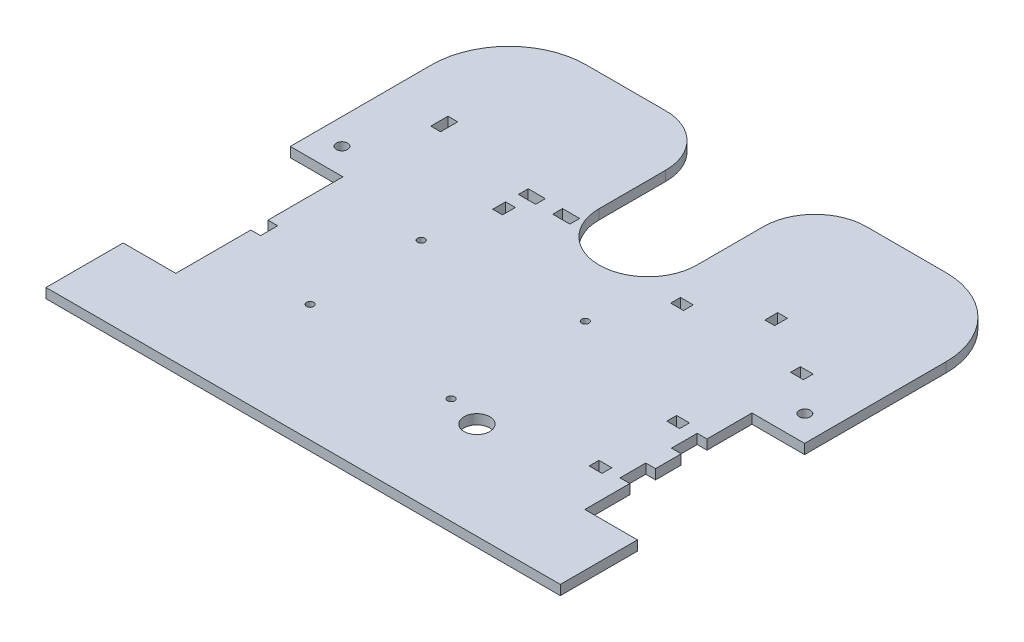
SolidWorks part; units mm, degrees
ref_plane "Front Plane" through (0, 0, 0) normal (0, 0, 1) x (1, 0, 0)
ref_plane "Top Plane" through (0, 0, 0) normal (0, 1, 0) x (1, 0, 0)
ref_plane "Right Plane" through (0, 0, 0) normal (1, 0, 0) x (0, 0, -1)
sketch "Sketch1" plane through (0, 0, 0) normal (0, 1, 0) x (1, 0, 0)
  line L1 (-127, 114.3) -> (127, 114.3)
  line L2 (-127, 114.3) -> (-127, -114.3)
  line L3 (-127, -114.3) -> (127, -114.3)
  line L4 (127, 114.3) -> (127, -114.3)
  line L5 (-127, 114.3) -> (127, -114.3) construction
  line L6 (-127, -114.3) -> (127, 114.3) construction
  point P0 (0, 0)
  dimension "D1" = 254
  dimension "D2" = 228.6
extrude "Boss-Extrude1" add sketch "Sketch1" along normal blind 4.826
sketch "Sketch2" plane through (0, 4.826, 0) normal (0, 1, 0) x (1, 0, 0)
  line L0 (-127, 114.3) -> (-127, -114.3) construction
  line L1 (-127, 6.35) -> (-101, 6.35)
  line L2 (-127, 6.35) -> (-127, -76.2)
  line L3 (-127, -76.2) -> (-101, -76.2)
  line L4 (-101, 6.35) -> (-101, -76.2)
  line L5 (127, -114.3) -> (127, 114.3) construction
  line L6 (127, 6.35) -> (101, 6.35)
  line L7 (127, 6.35) -> (127, -76.2)
  line L8 (127, -76.2) -> (101, -76.2)
  line L9 (101, 6.35) -> (101, -76.2)
  line L10 (-127, -114.3) -> (127, -114.3) construction
  dimension "D1" = 38.1
  dimension "D2" = 38.1
  dimension "D3" = 82.55
  dimension "D4" = 82.55
  dimension "D5" = 26
  dimension "D6" = 26
extrude "Cut-Extrude1" cut sketch "Sketch2" against normal blind 4.826
sketch "Sketch4" plane through (0, 4.826, 0) normal (0, 1, 0) x (1, 0, 0)
  line L0 (0, -114.3) -> (0, 114.3) construction
  line L1 (-127, -114.3) -> (127, -114.3) construction
  line L2 (127, 114.3) -> (-127, 114.3) construction
  line L3 (-127, 76.2) -> (-88.9, 76.2) construction
  line L4 (-127, 114.3) -> (-127, 6.35) construction
  line L5 (-88.9, 76.2) -> (-88.9, 114.3) construction
  line L6 (-127, 76.2) -> (-127, 114.3)
  line L7 (-127, 114.3) -> (-88.9, 114.3)
  line L8 (127, 76.2) -> (127, 114.3)
  line L9 (127, 114.3) -> (88.9, 114.3)
  arc A0 (-127, 76.2) -> (-88.9, 114.3) centre (-88.9, 76.2) cw
  arc A1 (127, 76.2) -> (88.9, 114.3) centre (88.9, 76.2) ccw
  dimension "D1" = 38.1
  dimension "D2" = 38.1
extrude "Cut-Extrude3" cut sketch "Sketch4" against normal blind 4.826
sketch "Sketch17" plane through (0, 0, 0) normal (0, -1, 0) x (1, 0, 0)
  circle A0 centre (114.3, -19.1646) radius 2.7781 construction
  circle A1 centre (-114.3, -19.1646) radius 2.7781 construction
  circle A2 centre (114.3, -19.1646) radius 2.7781
  circle A3 centre (-114.3, -19.1646) radius 2.7781
extrude "Cut-Extrude14" cut sketch "Sketch17" against normal through all
sketch "Sketch18" plane through (0, 4.826, 0) normal (0, 1, 0) x (1, 0, 0)
  line L0 (101, -53.975) -> (96.174, -53.975) construction
  line L1 (96.174, -41.275) -> (96.174, -53.975) construction
  line L2 (101, -41.275) -> (96.174, -41.275) construction
  line L3 (101, -41.275) -> (101, -53.975) construction
  line L4 (101, -15.875) -> (101, -28.575) construction
  line L5 (101, -15.875) -> (96.174, -15.875) construction
  line L6 (96.174, -15.875) -> (96.174, -28.575) construction
  line L7 (101, -28.575) -> (96.174, -28.575) construction
  line L8 (101, -53.975) -> (96.174, -53.975)
  line L9 (96.174, -41.275) -> (96.174, -53.975)
  line L10 (101, -41.275) -> (96.174, -41.275)
  line L11 (101, -41.275) -> (101, -53.975)
  line L12 (101, -15.875) -> (101, -28.575)
  line L13 (101, -15.875) -> (96.174, -15.875)
  line L14 (96.174, -15.875) -> (96.174, -28.575)
  line L15 (101, -28.575) -> (96.174, -28.575)
extrude "Cut-Extrude15" cut sketch "Sketch18" against normal through all
sketch "Sketch19" plane through (0, 4.826, 0) normal (0, 1, 0) x (1, 0, 0)
  line L0 (-101, -39.1583) -> (-101, -30.6917) construction
  line L1 (-101, -39.1583) -> (-96.174, -39.1583) construction
  line L2 (-96.174, -39.1583) -> (-96.174, -30.6917) construction
  line L3 (-101, -30.6917) -> (-96.174, -30.6917) construction
  line L4 (-101, 49.7417) -> (-101, 58.2083) construction
  line L5 (-101, 49.7417) -> (-96.174, 49.7417) construction
  line L6 (-96.174, 49.7417) -> (-96.174, 58.2083) construction
  line L7 (-101, 58.2083) -> (-96.174, 58.2083) construction
  line L8 (-101, -39.1583) -> (-101, -30.6917)
  line L9 (-101, -39.1583) -> (-96.174, -39.1583)
  line L10 (-96.174, -39.1583) -> (-96.174, -30.6917)
  line L11 (-101, -30.6917) -> (-96.174, -30.6917)
  line L12 (-101, 49.7417) -> (-101, 58.2083)
  line L13 (-101, 49.7417) -> (-96.174, 49.7417)
  line L14 (-96.174, 49.7417) -> (-96.174, 58.2083)
  line L15 (-101, 58.2083) -> (-96.174, 58.2083)
extrude "Cut-Extrude16" cut sketch "Sketch19" against normal through all
sketch "Sketch20" plane through (0, 0, 0) normal (0, -1, 0) x (1, 0, 0)
  line L0 (83.474, 51.689) -> (89.824, 51.689) construction
  line L1 (83.474, 56.515) -> (83.474, 51.689) construction
  line L2 (83.474, 56.515) -> (89.824, 56.515) construction
  line L3 (89.824, 56.515) -> (89.824, 51.689) construction
  line L4 (83.474, 13.335) -> (89.824, 13.335) construction
  line L5 (83.474, 18.161) -> (83.474, 13.335) construction
  line L6 (83.474, 18.161) -> (89.824, 18.161) construction
  line L7 (89.824, 18.161) -> (89.824, 13.335) construction
  line L8 (83.474, 51.689) -> (89.824, 51.689)
  line L9 (83.474, 56.515) -> (83.474, 51.689)
  line L10 (83.474, 56.515) -> (89.824, 56.515)
  line L11 (89.824, 56.515) -> (89.824, 51.689)
  line L12 (83.474, 13.335) -> (89.824, 13.335)
  line L13 (83.474, 18.161) -> (83.474, 13.335)
  line L14 (83.474, 18.161) -> (89.824, 18.161)
  line L15 (89.824, 18.161) -> (89.824, 13.335)
extrude "Cut-Extrude17" cut sketch "Sketch20" against normal blind 4.826
sketch "Sketch21" plane through (0, 4.826, 0) normal (0, 1, 0) x (1, 0, 0)
  circle A0 centre (-54.5489, -56.294) radius 1.778 construction
  circle A1 centre (-54.5489, -1.43) radius 1.778 construction
  circle A2 centre (20.6351, -61.882) radius 1.778 construction
  circle A3 centre (20.6351, 4.412) radius 1.778 construction
  circle A4 centre (-54.5489, -56.294) radius 1.778
  circle A5 centre (-54.5489, -1.43) radius 1.778
  circle A6 centre (20.6351, -61.882) radius 1.778
  circle A7 centre (20.6351, 4.412) radius 1.778
extrude "Cut-Extrude18" cut sketch "Sketch21" against normal through all
sketch "Sketch22" plane through (0, 4.826, 0) normal (0, 1, 0) x (1, 0, 0)
  circle A0 centre (37.849, -66.3327) radius 6.35
  circle A1 centre (20.6351, -61.882) radius 1.778 construction
  dimension "D1" = 12.7
  dimension "D2" = 17.78
extrude "Cut-Extrude19" cut sketch "Sketch22" against normal through all
sketch "Sketch24" plane through (0, 0, 0) normal (0, -1, 0) x (1, 0, 0)
  circle A0 centre (0, -55.982) radius 24.13 construction
  circle A1 centre (0, -55.982) radius 24.13
extrude "Cut-Extrude21" cut sketch "Sketch24" against normal through all
sketch "Sketch26" plane through (0, 4.826, 0) normal (0, 1, 0) x (1, 0, 0)
  line L0 (99.476, 38.1) -> (93.126, 38.1) construction
  line L1 (99.476, 38.1) -> (93.126, 38.1)
  line L2 (93.126, 33.274) -> (93.126, 38.1) construction
  line L3 (99.476, 33.274) -> (93.126, 33.274) construction
  line L4 (99.476, 33.274) -> (99.476, 38.1) construction
  line L5 (64.424, 49.276) -> (69.25, 49.276) construction
  line L6 (64.424, 55.626) -> (64.424, 49.276) construction
  line L7 (64.424, 55.626) -> (69.25, 55.626) construction
  line L8 (69.25, 55.626) -> (69.25, 49.276) construction
  line L9 (33.944, 38.1) -> (40.294, 38.1) construction
  line L10 (33.944, 38.1) -> (33.944, 33.274) construction
  line L11 (93.126, 33.274) -> (93.126, 38.1)
  line L12 (99.476, 33.274) -> (93.126, 33.274)
  line L13 (99.476, 33.274) -> (99.476, 38.1)
  line L14 (99.476, 38.1) -> (93.126, 38.1)
  line L15 (64.424, 49.276) -> (69.25, 49.276)
  line L16 (64.424, 55.626) -> (64.424, 49.276)
  line L17 (64.424, 55.626) -> (69.25, 55.626)
  line L18 (69.25, 55.626) -> (69.25, 49.276)
  line L19 (33.944, 38.1) -> (40.294, 38.1)
  line L20 (33.944, 38.1) -> (33.944, 33.274)
  line L21 (33.944, 33.274) -> (40.294, 33.274) construction
  line L22 (40.294, 38.1) -> (40.294, 33.274) construction
  line L23 (33.944, 33.274) -> (40.294, 33.274)
  line L24 (40.294, 38.1) -> (40.294, 33.274)
extrude "Cut-Extrude23" cut sketch "Sketch26" against normal through all contours L18 L17 L16 L15 | L24 L19 L20 L23 | L12 L13 L1 L11 region at (96.301, 4.826, -35.687) region at (66.837, 4.826, -52.451) region at (37.119, 4.826, -35.687)
sketch "Sketch27" plane through (0, 0, 0) normal (0, -1, 0) x (1, 0, 0)
  line L0 (-50.1365, -46.99) -> (-50.1365, -42.164) construction
  line L1 (-50.1365, -46.99) -> (-50.1365, -42.164)
  line L2 (-41.6699, -46.99) -> (-50.1365, -46.99) construction
  line L3 (-41.6699, -46.99) -> (-50.1365, -46.99)
  line L4 (-41.6699, -42.164) -> (-50.1365, -42.164) construction
  line L5 (-41.6699, -42.164) -> (-50.1365, -42.164)
  line L6 (-41.6699, -42.164) -> (-41.6699, -46.99) construction
  line L7 (-24.7365, -46.99) -> (-33.2032, -46.99) construction
  line L8 (-33.2032, -42.164) -> (-33.2032, -46.99) construction
  line L9 (-24.7365, -42.164) -> (-33.2032, -42.164) construction
  line L10 (-24.7365, -46.99) -> (-24.7365, -42.164) construction
  line L11 (-50.1365, -29.464) -> (-50.1365, -35.814) construction
  line L12 (-45.3105, -35.814) -> (-50.1365, -35.814) construction
  line L13 (-45.3105, -29.464) -> (-45.3105, -35.814) construction
  line L14 (-45.3105, -29.464) -> (-50.1365, -29.464) construction
  line L15 (-41.6699, -42.164) -> (-41.6699, -46.99)
  line L16 (-24.7365, -46.99) -> (-33.2032, -46.99)
  line L17 (-33.2032, -42.164) -> (-33.2032, -46.99)
  line L18 (-24.7365, -42.164) -> (-33.2032, -42.164)
  line L19 (-24.7365, -46.99) -> (-24.7365, -42.164)
  line L20 (-50.1365, -29.464) -> (-50.1365, -35.814)
  line L21 (-45.3105, -35.814) -> (-50.1365, -35.814)
  line L22 (-45.3105, -29.464) -> (-45.3105, -35.814)
  line L23 (-45.3105, -29.464) -> (-50.1365, -29.464)
extrude "Cut-Extrude24" cut sketch "Sketch27" against normal through all
sketch "Sketch28" plane through (0, 4.826, 0) normal (0, 1, 0) x (1, 0, 0)
  line L0 (-24.13, 55.982) -> (-24.13, 114.3)
  line L1 (88.9, 114.3) -> (-88.9, 114.3) construction
  line L2 (24.13, 55.982) -> (24.13, 114.3)
  line L3 (24.13, 114.3) -> (-24.13, 114.3)
  circle A0 centre (0, 55.982) radius 24.13 construction
  circle A1 centre (0, 55.982) radius 24.13
extrude "Cut-Extrude25" cut sketch "Sketch28" against normal through all contours A1 L2 L3 L0 region at (0, 4.826, -94.2484)
fillet "Fillet1" radius 25.4 2 edges at (-24.13, 2.413, -114.3) (24.13, 2.413, -114.3)
equation "\"MDF\"= 0.19in"
equation "\"GenDiameter\"= 60mm"
equation "\"GenCutDiameter\" = 1.8in"
equation "\"GenCutDistance\" = 1"
equation "\"TowerHeight\" = 6in"
equation "\"TowerFrontBase\" = 3in"
equation "\"FunnelHeight\" = 1in"
equation "\"FunnelAngle\" = 20"
equation "\"TowerSideBase\" = 3in"
equation "\"BaseLength\" = 9in"
equation "\"BaseWidth\" = 10in"
equation "\"WheelHoleLength\" = 3.25in"
equation "\"WheelHoleWidth\" = 26mm"
equation "\"DropLength\" = 1in"
equation "\"D1@Sketch1\"=\"BaseWidth\""
equation "\"D2@Sketch1\"=\"BaseLength\""
equation "\"D1@Boss-Extrude1\"=\"MDF\""
equation "\"WheelHoleFromBack\" = 1.5in"
equation "\"D1@Sketch2\"=\"WheelHoleFromBack\""
equation "\"D2@Sketch2\"=\"WheelHoleFromBack\""
equation "\"D3@Sketch2\"=\"WheelHoleLength\""
equation "\"D4@Sketch2\"=\"WheelHoleLength\""
equation "\"D5@Sketch2\"=\"WheelHoleWidth\""
equation "\"D6@Sketch2\"=\"WheelHoleWidth\""
equation "\"D1@Cut-Extrude1\"=\"MDF\""
equation "\"DropWidth\" = 8.5in"
equation "\"BumperWidth\" = 2in"
equation "\"D1@Cut-Extrude3\"=\"MDF\""
equation "\"DropWidthTop\" = 0in"
equation "\"D1@Cut-Extrude17\"=\"MDF\""
